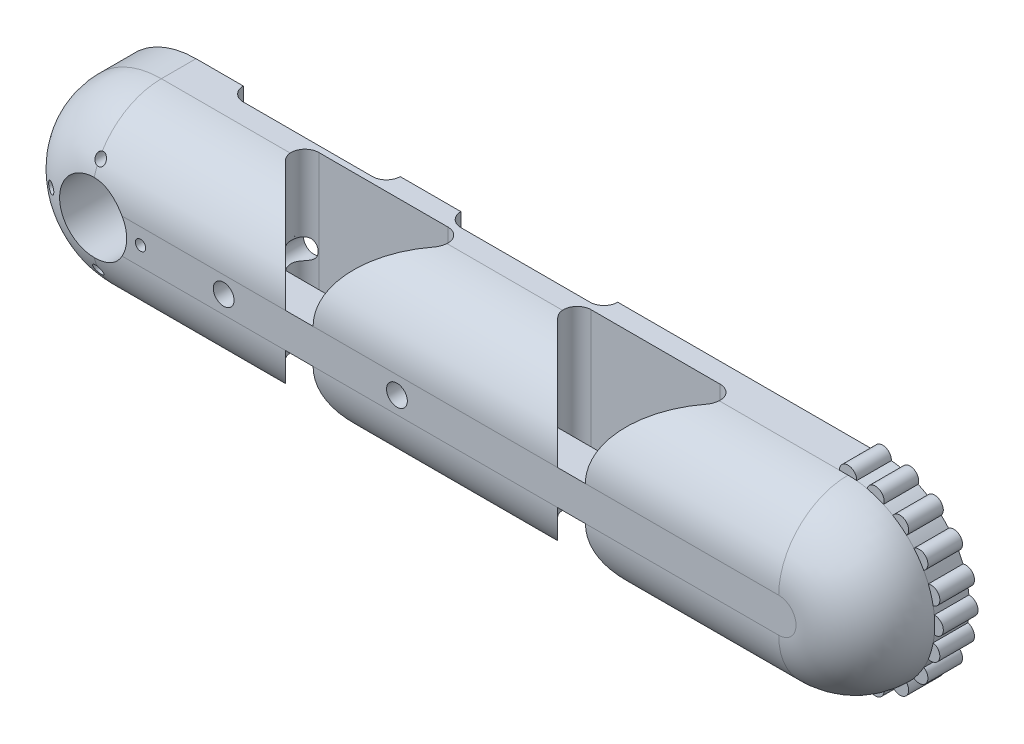
SolidWorks part; units mm, degrees
ref_plane "Ebene vorne" through (0, 0, 0) normal (0, 0, 1) x (1, 0, 0)
ref_plane "Ebene oben" through (0, 0, 0) normal (0, 1, 0) x (1, 0, 0)
ref_plane "Ebene rechts" through (0, 0, 0) normal (1, 0, 0) x (0, 0, -1)
sketch "Skizze1" plane through (0, 0, 0) normal (0, 0, 1) x (1, 0, 0)
  line L1 (15.1829, 0) -> (114.2485, 0)
  line L3 (15.1829, 25) -> (114.2485, 25)
  circle A0 centre (15.1829, 12.5) radius 5
  arc A1 (15.1829, 25) -> (15.1829, 0) centre (15.1829, 12.5) ccw
  arc A2 (114.2485, 0) -> (114.2485, 25) centre (114.2485, 12.5) ccw
  dimension "D3" = 10
extrude "Aufsatz-Linear austragen1" add sketch "Skizze1" along normal blind 15
sketch "Skizze3" plane through (0, 0, 0) normal (0, 0, -1) x (-1, 0, 0)
  circle A0 centre (-15.1829, 12.5) radius 10.45
  dimension "D1" = 20.9
extrude "Schnitt-Linear austragen2" cut sketch "Skizze3" against normal blind 2
fillet "Verrundung2" radius 10 4 edges at (64.7157, 25, 15) (64.7157, 0, 15) (2.6829, 12.5, 15) (126.7485, 12.5, 15)
sketch "Skizze9" plane through (0, 25, 0) normal (0, 1, 0) x (1, 0, 0)
  line L3 (22.5971, 1.4142) -> (31.9108, 10.7279)
  line L4 (34.7392, 10.7279) -> (44.0529, 1.4142)
  line L5 (42.6387, -2) -> (24.0113, -2)
  line L6 (53.9877, 1.4142) -> (63.3015, 10.7279)
  line L7 (66.1299, 10.7279) -> (75.4436, 1.4142)
  line L8 (74.0294, -2) -> (55.402, -2)
  line L9 (15.1829, -5) -> (114.2485, -5) construction
  line L10 (101.1299, 1.4142) -> (110.4437, 10.7279)
  line L11 (113.2721, 10.7279) -> (122.5858, 1.4142)
  line L12 (121.1716, -2) -> (102.5442, -2)
  line L13 (55.8015, -6.2742) -> (46.4877, -15.5879)
  line L14 (43.6593, -15.5879) -> (34.3456, -6.2742)
  line L15 (35.7598, -2.86) -> (54.3872, -2.86)
  line L16 (95.0857, -6.2742) -> (85.772, -15.5879)
  line L17 (82.9436, -15.5879) -> (73.6299, -6.2742)
  line L18 (75.0441, -2.86) -> (93.6715, -2.86)
  line L19 (114.2485, 0) -> (15.1829, 0) construction
  line L20 (15.1829, -5) -> (15.1829, 0) construction
  arc A0 (110.4437, 10.7279) -> (113.2721, 10.7279) centre (111.8579, 9.3137) cw
  arc A1 (122.5858, 1.4142) -> (121.1716, -2) centre (121.1716, 0) cw
  arc A2 (101.1299, 1.4142) -> (102.5442, -2) centre (102.5442, 0) ccw
  arc A3 (95.0857, -6.2742) -> (93.6715, -2.86) centre (93.6715, -4.86) ccw
  arc A4 (73.6299, -6.2742) -> (75.0441, -2.86) centre (75.0441, -4.86) cw
  arc A5 (85.772, -15.5879) -> (82.9436, -15.5879) centre (84.3578, -14.1737) cw
  arc A6 (75.4436, 1.4142) -> (74.0294, -2) centre (74.0294, 0) cw
  arc A7 (53.9877, 1.4142) -> (55.402, -2) centre (55.402, 0) ccw
  arc A8 (63.3015, 10.7279) -> (66.1299, 10.7279) centre (64.7157, 9.3137) cw
  arc A9 (55.8015, -6.2742) -> (54.3872, -2.86) centre (54.3872, -4.86) ccw
  arc A10 (46.4877, -15.5879) -> (43.6593, -15.5879) centre (45.0735, -14.1737) cw
  arc A11 (34.3456, -6.2742) -> (35.7598, -2.86) centre (35.7598, -4.86) cw
  arc A12 (44.0529, 1.4142) -> (42.6387, -2) centre (42.6387, 0) cw
  arc A13 (22.5971, 1.4142) -> (24.0113, -2) centre (24.0113, 0) ccw
  arc A14 (31.9108, 10.7279) -> (34.7392, 10.7279) centre (33.325, 9.3137) cw
  point P23 (64.7157, -2)
  point P24 (64.7157, -5)
  point P27 (111.8579, 12.1421)
  point P30 (126, -2)
  point P33 (97.7157, -2)
  point P38 (70.2157, -2.86)
  point P41 (84.3578, -17.0021)
  point P44 (78.8578, -2)
  point P47 (50.5735, -2)
  point P50 (64.7157, 12.1421)
  point P55 (45.0735, -17.0021)
  point P58 (30.9314, -2.86)
  point P63 (19.1829, -2)
  point P66 (33.325, 12.1421)
  dimension "D26" = 2
  dimension "D1" = 90
  dimension "D2" = 45
  dimension "D3" = 20
  dimension "D4" = 3
  dimension "D5" = 3
  dimension "D6" = 90
  dimension "D7" = 45
  dimension "D8" = 20
  dimension "D9" = 2.86
  dimension "D10" = 2.86
  dimension "D11" = 3
  dimension "D12" = 4
  dimension "D14" = 90
  dimension "D15" = 45
  dimension "D16" = 20
  dimension "D17" = 0
  dimension "D18" = 5.5
  dimension "D19" = 5.5
  dimension "D20" = 90
  dimension "D21" = 45
  dimension "D22" = 20
  dimension "D23" = 20
  dimension "D24" = 90
  dimension "D25" = 45
extrude "Schnitt-Linear austragen7" cut sketch "Skizze9" against normal blind 37
sketch "Skizze10" plane through (0, 0, 2) normal (0, 0, -1) x (-1, 0, 0)
  circle A0 centre (-15.3506, 19.498) radius 0.75
  circle A1 centre (-14.995, 5.5025) radius 0.75
  circle A2 centre (-8.1846, 12.3471) radius 0.75
  circle A3 centre (-22.1801, 12.6957) radius 0.75
  circle A4 centre (-15.1829, 12.5) radius 5 construction
  dimension "D1" = 7
  dimension "D2" = 7
  dimension "D3" = 7
  dimension "D4" = 7
  dimension "D5" = 1.5
  dimension "D6" = 1.5
  dimension "D7" = 1.5
  dimension "D8" = 1.5
extrude "Schnitt-Linear austragen8" cut sketch "Skizze10" against normal blind 37
sketch "Skizze11" plane through (0, 0, 15) normal (0, 0, 1) x (1, 0, 0)
  circle A0 centre (34.1695, 12.5609) radius 1.5
  circle A1 centre (59.1693, 12.4603) radius 1.5
  dimension "D1" = 25
  dimension "D3" = 3
  dimension "D4" = 3
extrude "Schnitt-Linear austragen9" cut sketch "Skizze11" against normal blind 37
sketch "Skizze12" plane through (0, 0, 0) normal (0, 0, -1) x (-1, 0, 0)
  line L0 (-76.0294, 0) -> (-100.5442, 0) construction
  line L1 (-114.2485, 25) -> (-97.1815, 25)
  line L3 (-114.2485, 0) -> (-97.1815, 0)
  line L4 (-97.1815, 25) -> (-97.1815, 0)
  arc A0 (-114.2485, 25) -> (-114.2485, 0) centre (-114.2485, 12.5) ccw
extrude "Aufsatz-Linear austragen2" add sketch "Skizze12" against normal blind 5
sketch "Skizze13" plane through (0, 0, 0) normal (0, 0, -1) x (-1, 0, 0)
  circle A0 centre (-114.2485, 0) radius 1.25
  circle A1 centre (-118.1969, 0.64) radius 1.25
  arc A2 (-114.2485, 25) -> (-114.2485, 0) centre (-114.2485, 12.5) ccw construction
  circle A3 centre (-121.7411, 2.4945) radius 1.25
  circle A4 centre (-124.518, 5.3735) radius 1.25
  circle A5 centre (-126.2433, 8.9823) radius 1.25
  circle A6 centre (-126.7485, 12.5) radius 1.25
  circle A7 centre (-126.2433, 16.0177) radius 1.25
  circle A8 centre (-124.518, 19.6265) radius 1.25
  circle A9 centre (-114.2485, 25) radius 1.25
  circle A10 centre (-121.7411, 22.5055) radius 1.25
  circle A11 centre (-118.1969, 24.36) radius 1.25
  dimension "D1" = 2.5
  dimension "D2" = 2.5
  dimension "D3" = 2.5
  dimension "D4" = 2.5
  dimension "D5" = 2.5
  dimension "D6" = 2.5
  dimension "D7" = 2.5
  dimension "D8" = 2.5
  dimension "D9" = 2.5
  dimension "D10" = 2.5
  dimension "D11" = 2.5
  dimension "D12" = 4
  dimension "D13" = 4
  dimension "D14" = 4
  dimension "D15" = 4
  dimension "D16" = 4
  dimension "D17" = 4
  dimension "D18" = 4
  dimension "D19" = 4
extrude "Aufsatz-Linear austragen3" add sketch "Skizze13" against normal blind 5
sketch "Skizze14" plane through (0, 0, 15) normal (0, 0, 1) x (1, 0, 0)
  line L0 (82.3557, 15) -> (47.0757, 15) construction
  line L1 (67.6889, 15) -> (101.1697, 15)
  line L2 (67.6889, 15) -> (67.6889, 10)
  line L3 (67.6889, 10) -> (101.1697, 10)
  line L4 (101.1697, 15) -> (101.1697, 10)
  line L5 (86.3599, 10) -> (114.2485, 10) construction
  line L6 (43.0714, 15) -> (19.513, 15) construction
  line L7 (36.9219, 15) -> (54.7479, 15)
  line L8 (36.9219, 15) -> (36.9219, 10)
  line L9 (36.9219, 10) -> (54.7479, 10)
  line L10 (54.7479, 15) -> (54.7479, 10)
  line L11 (47.0757, 10) -> (82.3557, 10) construction
extrude "Aufsatz-Linear austragen4" add sketch "Skizze14" against normal blind 5
